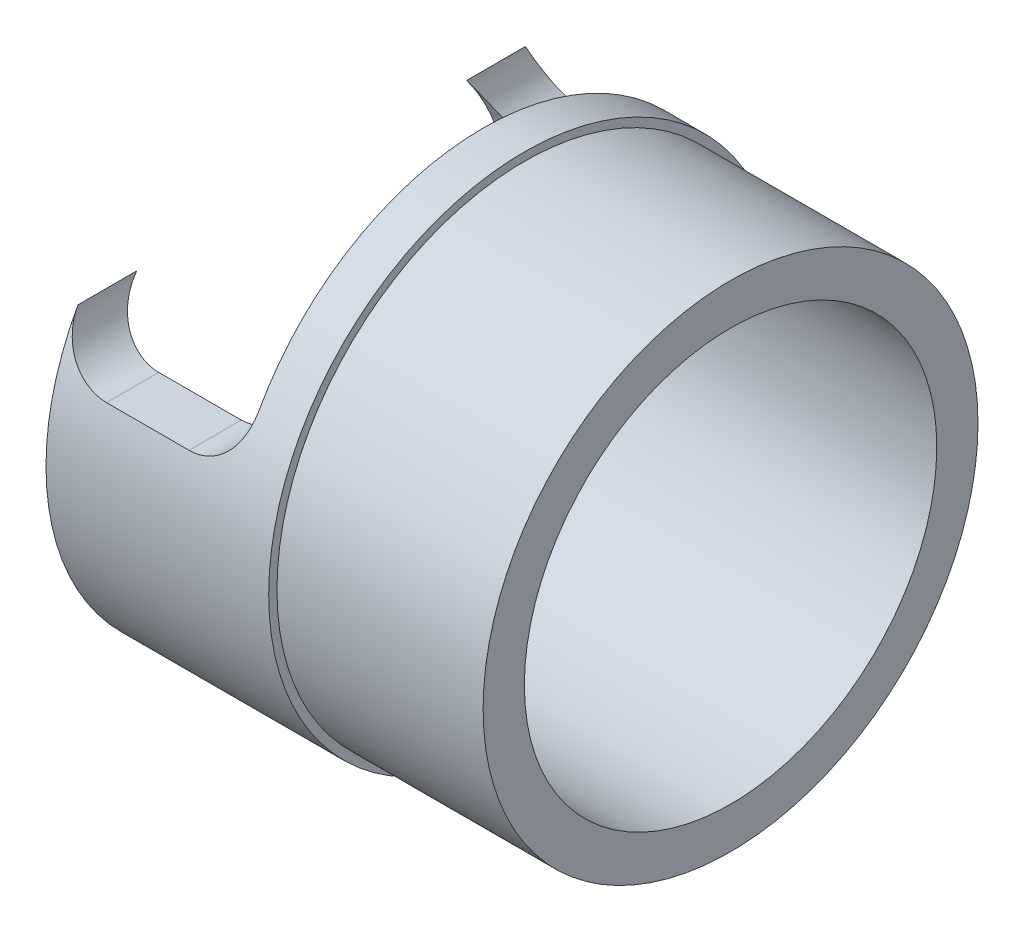
SolidWorks part; units mm, degrees
ref_plane "Front Plane" through (0, 0, 0) normal (0, 0, 1) x (1, 0, 0)
ref_plane "Top Plane" through (0, 0, 0) normal (0, 1, 0) x (1, 0, 0)
ref_plane "Right Plane" through (0, 0, 0) normal (1, 0, 0) x (0, 0, -1)
sketch "Sketch1" plane through (0, 0, 0) normal (0, 0, 1) x (1, 0, 0)
  line L0 (-49, 0) -> (49, 0) construction
  line L1 (49, 0) -> (49, 25) construction
  line L2 (49, 25) -> (19, 25)
  line L3 (19, 25) -> (19, 31)
  line L4 (19, 31) -> (24, 31)
  line L5 (24, 31) -> (24, 30)
  line L6 (24, 30) -> (49, 30)
  line L7 (49, 30) -> (49, 25)
revolve "Revolve1" add sketch "Sketch1" angle 360 about L0
sketch "Sketch3" plane through (19, 0, 0) normal (-1, 0, 0) x (0, 0, 1)
  circle A1 centre (0, 0) radius 31
  circle A2 centre (0, 0) radius 31
  circle A3 centre (0, 0) radius 25
  circle A4 centre (0, 0) radius 31
  circle M2 centre (0, 0) radius 25
  circle M3 centre (0, 0) radius 31
  dimension "D1" = 0
extrude "Boss-Extrude1" add sketch "Sketch3" along normal blind 22 contours M3 M2 region at (19, 0, -30.1232)
sketch "Sketch4" plane through (0, 0, 0) normal (0, 0, 1) x (1, 0, 0)
  line L0 (-3, 31) -> (19, 31)
  line L1 (24, 31) -> (-3, 31) construction
  line L2 (-3, 31) -> (-3, 15)
  line L3 (-3, 31) -> (-3, -31) construction
  line L4 (3, 9) -> (13, 9)
  line L5 (19, 15) -> (19, 31)
  arc A0 (13, 9) -> (19, 15) centre (13, 15) ccw
  arc A1 (3, 9) -> (-3, 15) centre (3, 15) cw
  point P13 (-3, 9)
  dimension "D1" = 6
extrude "Cut-Extrude1" cut sketch "Sketch4" against normal through all both and the other way through all
sketch "Sketch10" plane through (0, 0, 0) normal (0, 0, 1) x (1, 0, 0)
  line L0 (49, 30) -> (49, 10.2608) construction
  line L1 (49, -30) -> (49, 30) construction
  line L2 (49, 30) -> (49, -30) construction
  line L3 (49, 0) -> (-60.8461, 0) construction
  line L4 (-3, 0) -> (-3, 31.9128)
  line L5 (-3, 15) -> (-3, -31) construction
  line L6 (-17, 19) -> (-3, 19)
  line L7 (-17, 38) -> (-17, 37.9958)
  line L8 (-24.9958, 30) -> (-24.9958, 0)
  line L9 (-28, 30) -> (-28, 0)
  line L10 (-17, 22.0042) -> (-17, 0)
  arc A0 (-17, 22.0042) -> (-24.9958, 30) centre (-17, 30) ccw
  arc A1 (-8.2173, 36.623) -> (-28, 30) centre (-17, 30) ccw
  arc A2 (-9.4502, 38) -> (-3, 31.9128) centre (22.324, 65.2077) ccw
